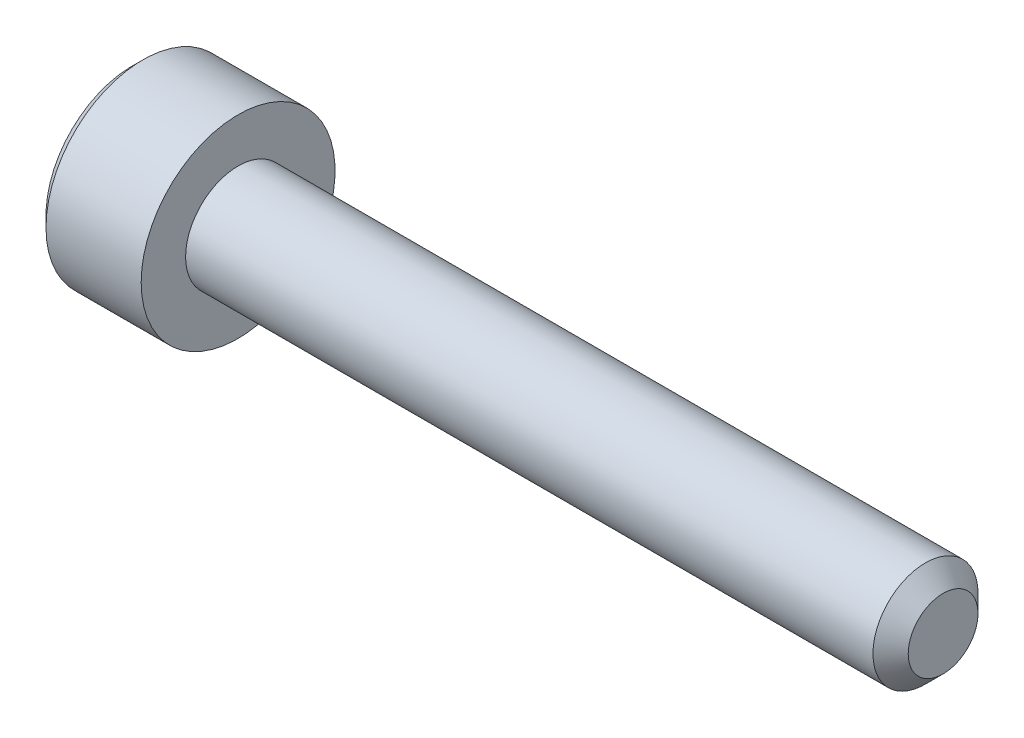
SolidWorks part; units mm, degrees
material "AISI Type 316L stainless steel"
ref_plane "Front Plane" through (0, 0, 0) normal (0, 0, 1) x (1, 0, 0)
ref_plane "Top Plane" through (0, 0, 0) normal (0, 1, 0) x (1, 0, 0)
ref_plane "Right Plane" through (0, 0, 0) normal (1, 0, 0) x (0, 0, -1)
sketch "Sketch1" plane through (0, 0, 0) normal (0, 0, 1) x (1, 0, 0)
  line L0 (-88.7055, 0) -> (96.9812, 0) construction
  line L1 (0, 0) -> (0, 2.75)
  line L2 (0, 2.75) -> (3, 2.75)
  line L4 (23, 0) -> (23, 1.49)
  line L5 (23, 1.49) -> (3, 1.49)
  line L6 (3, 1.49) -> (3, 2.75)
  line L7 (0, 0) -> (23, 0)
  dimension "D1" = 20
  dimension "D2" = 3
  dimension "D3" = 2.75
  dimension "D4" = 1.49
revolve "Revolve1" add sketch "Sketch1" angle 360 about L0
chamfer "Chamfer1" distance 0.5 angle 45 1 edges at (23, 0, 1.49)
chamfer "Chamfer2" distance 0.3 angle 45 1 edges at (0, 0, 2.75)
sketch "Sketch3" plane through (0, 0, 0) normal (1, 0, 0) x (0, 0, -1)
  line L1 (-1.4434, 0) -> (-0.7217, -1.25)
  line L2 (-0.7217, -1.25) -> (0.7217, -1.25)
  line L3 (0.7217, -1.25) -> (1.4434, 0)
  line L4 (1.4434, 0) -> (0.7217, 1.25)
  line L5 (0.7217, 1.25) -> (-0.7217, 1.25)
  line L6 (-0.7217, 1.25) -> (-1.4434, 0)
  circle A0 centre (0, 0) radius 1.25 construction
extrude "Cut-Extrude1" cut sketch "Sketch3" along normal blind 2.5
chamfer "Chamfer3" distance 0.3 angle 45 6 edges at (0, 1.25, 0) (0, 0.625, 1.0825) (0, -0.625, 1.0825) (0, -1.25, 0) (0, -0.625, -1.0825) (0, 0.625, -1.0825)
sketch "Sketch5" plane through (23, 0, 0) normal (1, 0, 0) x (0, 0, -1)
  circle A0 centre (0, 0) radius 1.49
curve "Helix/Spiral1" pitch 0.5 height 20 turns 40
sketch "Sketch8" plane through (0, 0, 0) normal (0, 1, 0) x (1, 0, 0)
  line L0 (23, 1.49) -> (23, 1.1111) construction
  line L1 (23.0625, 1.2194) -> (23.3281, 1.6794)
  line L2 (23.3281, 1.6794) -> (22.6719, 1.6794)
  line L3 (22.6719, 1.6794) -> (22.9375, 1.2194)
  line L4 (23, -0.99) -> (23, 0.99) construction
  circle A0 centre (23, 1.49) radius 0.1894 construction
  arc A1 (23.0625, 1.2194) -> (22.9375, 1.2194) centre (23, 1.2555) cw
  dimension "D2" = 0.0722
  dimension "D1" = 0.3789
sweep "Cut-Sweep1" [suppressed] cut profiles "Sketch8" path "Helix/Spiral1"
equation "\"length\" = 20"
